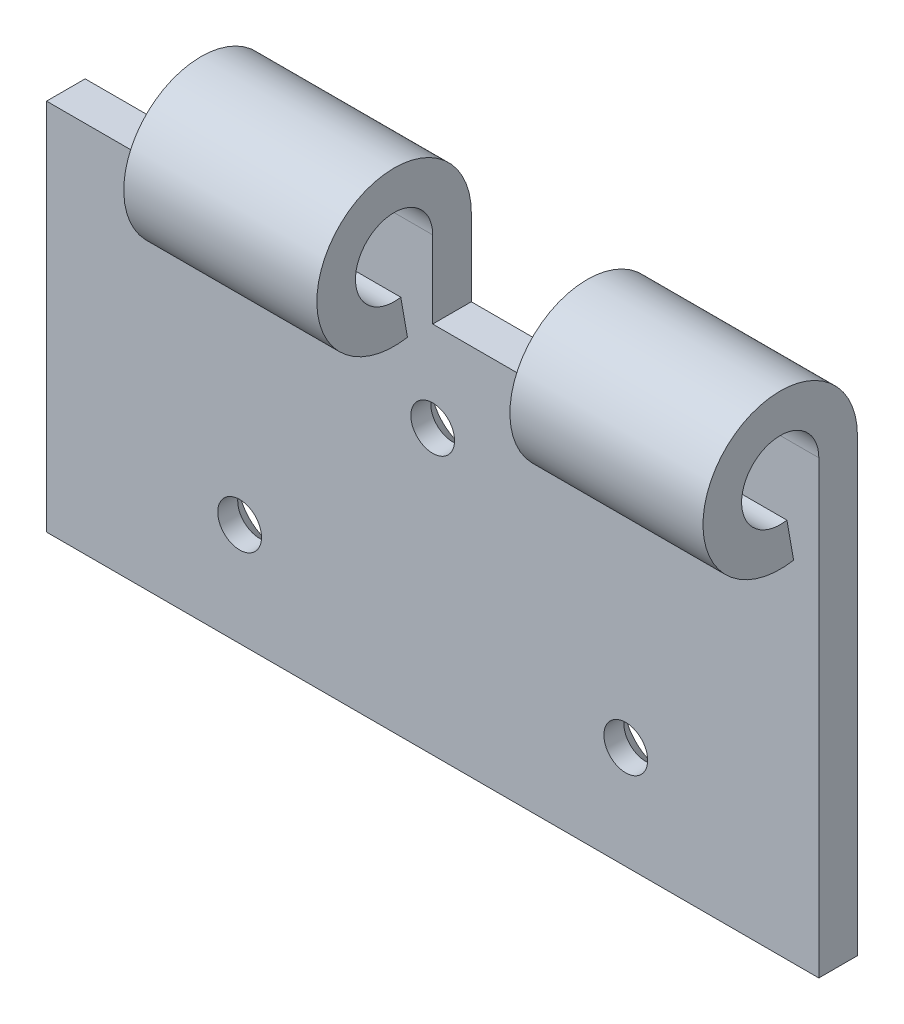
SolidWorks part; units mm, degrees
material "PET"
ref_plane "Front Plane" through (0, 0, 0) normal (0, 0, 1) x (1, 0, 0)
ref_plane "Top Plane" through (0, 0, 0) normal (0, 1, 0) x (1, 0, 0)
ref_plane "Right Plane" through (0, 0, 0) normal (1, 0, 0) x (0, 0, -1)
sketch "Sketch1" plane through (0, 0, 0) normal (0, 0, 1) x (1, 0, 0)
  line L1 (-30, -17.5) -> (30, -17.5)
  line L2 (-30, -17.5) -> (-30, 17.5)
  line L3 (-30, 17.5) -> (30, 17.5)
  line L4 (30, -17.5) -> (30, 17.5)
  line L5 (-30, -17.5) -> (30, 17.5) construction
  line L6 (-30, 17.5) -> (30, -17.5) construction
  point P0 (0, 0)
  dimension "D2" = 35
  dimension "D3" = 60
extrude "Boss-Extrude1" add sketch "Sketch1" along normal blind 3 contours L1 L4 L3 L2 region at (0, 0, 0)
sketch "Sketch5" plane through (30, 0, 0) normal (1, 0, 0) x (0, 0, -1)
  line L0 (0, 17.5) -> (-6, 17.5) construction
  line L1 (0, -17.5) -> (0, 17.5) construction
  line L2 (-6, 17.5) -> (-5.4791, 14.5456) construction
  line L5 (-3, -17.5) -> (-3, 17.5) construction
  line L6 (-5.4791, 14.5456) -> (-4.9581, 11.5912)
  line L7 (-3, 17.5) -> (-3, 12.3038)
  arc A0 (-3, 12.3038) -> (-4.9581, 11.5912) centre (-6, 17.5) ccw
  arc A1 (-3, 17.5) -> (-5.4791, 14.5456) centre (-6, 17.5) ccw
  circle A2 centre (-6, 17.5) radius 3 construction
  circle A3 centre (-6, 17.5) radius 6 construction
  dimension "D1" = 6
  dimension "D3" = 80
  dimension "D2" = 3
extrude "Boss-Extrude2" add sketch "Sketch5" against normal up to surface (60 mm away) up to face at (-30, 0, 1.5)
sketch "Sketch9" plane through (-12, 0, 3) normal (0, 0, -1) x (-1, 0, 0)
  line L6 (18, 23.5) -> (-42, 23.5) construction
  line L9 (-27, 23.5) -> (-12, 23.5)
  line L11 (-27, 23.5) -> (-27, 11.5)
  line L13 (-27, 11.5) -> (-12, 11.5)
  line L19 (-12, 23.5) -> (-12, 11.5)
  line L20 (18, -17.5) -> (18, 17.5) construction
  line L21 (3, 23.5) -> (18, 23.5)
  line L22 (3, 23.5) -> (3, 11.5)
  line L23 (3, 11.5) -> (18, 11.5)
  line L24 (18, 23.5) -> (18, 11.5)
  dimension "D1" = 15
  dimension "D2" = 15
  dimension "D3" = 12
extrude "Cut-Extrude4" cut sketch "Sketch9" along normal through all both and the other way through all
sketch "Sketch2" plane through (0, 0, 0) normal (0, 0, 1) x (1, 0, 0)
  line L0 (-15, 17.5) -> (0, 17.5) construction
  line L1 (0, -6.6) -> (0, 6.6) construction
  point P0 (0, 4.5)
  point P2 (-15, -9.5)
  point P16 (15, -9.5)
  dimension "D1" = 14
  dimension "D2" = 30
  dimension "D6" = 13
hole_wizard "CSK for M3 Countersunk Flat Head Screw1" positions "Sketch2" profile "Sketch3" countersink size "M3" standard "ISO"
sketch "Sketch3" plane through (0, 4.5, 0) normal (1, 0, 0) x (0, 1, 0)
  line L0 (0, 0) -> (0, 4.0215)
  line L1 (0, 4.0215) -> (1.7, 3)
  line L2 (1.7, 3) -> (1.7, 1.45)
  line L3 (1.7, 1.45) -> (3.15, 0)
  line L5 (3.15, 0) -> (0, 0)
  line L6 (-1.7, 1.45) -> (-3.15, 0) construction
  line L10 (0, 4.0215) -> (-1.7, 3) construction
  line L11 (0, -6.35) -> (0, 107.95) construction
  dimension "Hole Dia." = 3.4
  dimension "Hole Depth" = 3
  dimension "Near C'Sink Dia." = 6.3
  dimension "Near C'Sink Angle" = 90
  dimension "Drill Angle" = 118
